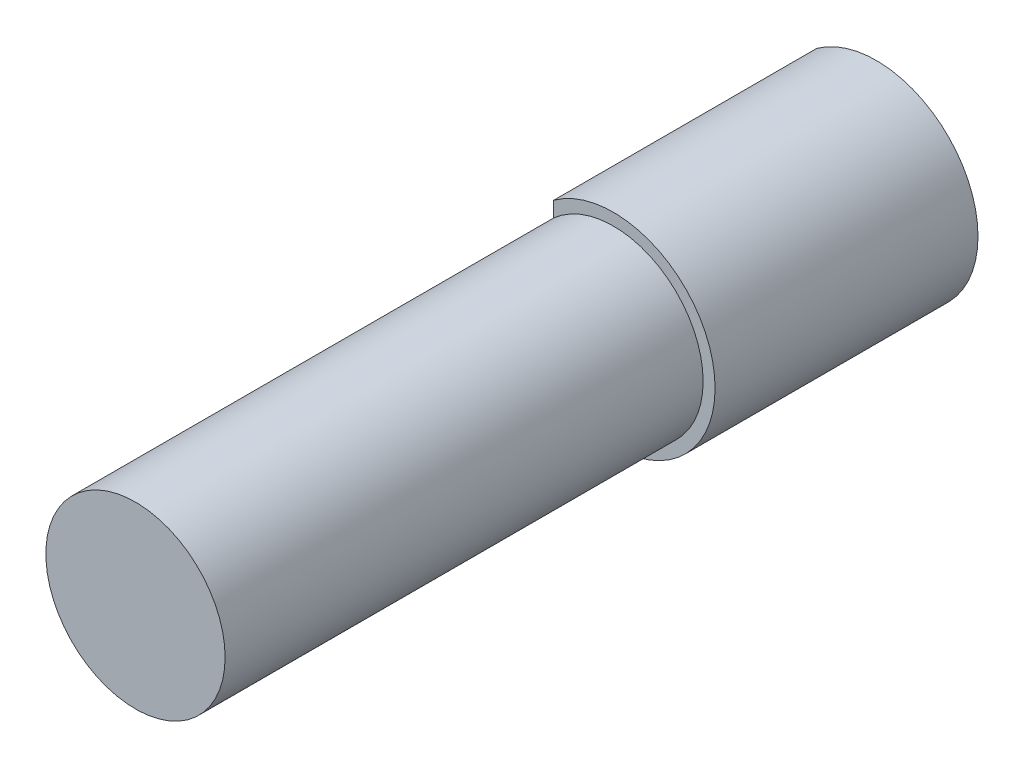
SolidWorks part; units mm, degrees
ref_plane "Front Plane" through (0, 0, 0) normal (0, 0, 1) x (1, 0, 0)
ref_plane "Top Plane" through (0, 0, 0) normal (0, 1, 0) x (1, 0, 0)
ref_plane "Right Plane" through (0, 0, 0) normal (1, 0, 0) x (0, 0, -1)
sketch "Sketch1" plane through (0, 0, 0) normal (0, 0, 1) x (1, 0, 0)
  line L0 (-2.5, 3.4369) -> (-2.5, -3.4369)
  arc A0 (-2.5, -3.4369) -> (-2.5, 3.4369) centre (0, 0) ccw
  dimension "D1" = 2.5
  dimension "D2" = 8.5
extrude "Boss-Extrude1" add sketch "Sketch1" along normal blind 10
sketch "Sketch2" plane through (0, 0, 10) normal (0, 0, 1) x (1, 0, 0)
  circle A0 centre (0, 0) radius 4.25
extrude "Boss-Extrude2" add sketch "Sketch2" along normal blind 20
sketch "Sketch3" plane through (0, 0, 0) normal (0, 0, -1) x (-1, 0, 0)
  line L1 (2.5, -3.4369) -> (2.5, 3.4369)
  line L2 (2.5, -3.4369) -> (2.5, 3.4369)
  arc A1 (2.5, 3.4369) -> (2.5, -3.4369) centre (0, 0) ccw
  arc A2 (2.5, 3.4369) -> (2.5, -3.4369) centre (0, 0) ccw
  dimension "D1" = 0
extrude "Boss-Extrude3" add sketch "Sketch3" along normal blind 1
sketch "Sketch5" plane through (0, 0, 30) normal (0, 0, 1) x (1, 0, 0)
  circle A0 centre (0, 0) radius 3.75
  circle A1 centre (0, 0) radius 4.25
  circle A2 centre (0, 0) radius 4.25
  dimension "D1" = 0
  dimension "D2" = 0.5
extrude "Cut-Extrude1" cut sketch "Sketch5" against normal up to surface (20 mm away) up to face at (-2.5, 3.4369, 10)
